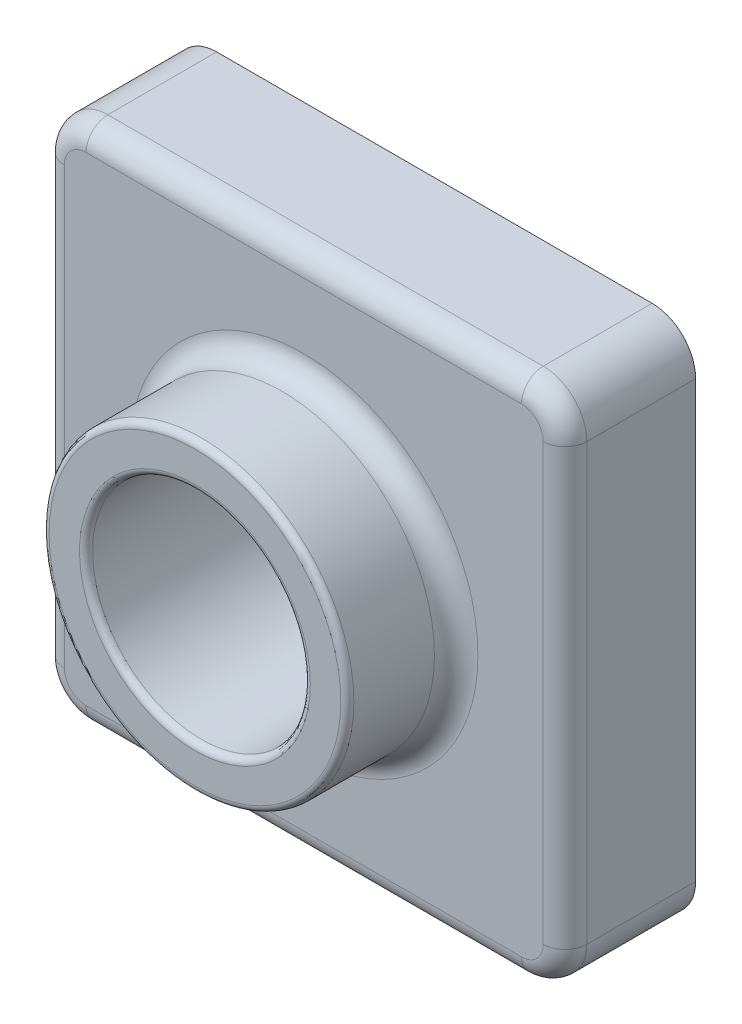
SolidWorks part; units mm, degrees
ref_plane "Front Plane" through (0, 0, 0) normal (0, 0, 1) x (1, 0, 0)
ref_plane "Top Plane" through (0, 0, 0) normal (0, 1, 0) x (1, 0, 0)
ref_plane "Right Plane" through (0, 0, 0) normal (1, 0, 0) x (0, 0, -1)
sketch "Sketch1" plane through (0, 0, 0) normal (0, 0, 1) x (1, 0, 0)
  line L0 (0, 60) -> (0, -60) construction
  line L1 (-60, 60) -> (60, 60)
  line L2 (-60, 60) -> (-60, -60)
  line L3 (-60, -60) -> (60, -60)
  line L4 (60, 60) -> (60, -60)
  line L6 (-60, 0) -> (60, 0) construction
  dimension "D1" = 120
  dimension "D2" = 120
extrude "Boss-Extrude1" add sketch "Sketch1" along normal blind 30
sketch "Sketch2" plane through (0, 0, 30) normal (0, 0, 1) x (1, 0, 0)
  circle A0 centre (0, 0) radius 35
  dimension "D1" = 70
extrude "Boss-Extrude2" add sketch "Sketch2" along normal blind 25
sketch "Sketch3" plane through (0, 0, 55) normal (0, 0, 1) x (1, 0, 0)
  circle A0 centre (0, 0) radius 25
  dimension "D1" = 50
extrude "Cut-Extrude1" cut sketch "Sketch3" against normal blind 76
fillet "Fillet1" radius 5 5 edges at (0, 60, 30) (60, 0, 30) (0, -60, 30) (-60, 0, 30) (35, 0, 30)
fillet "Fillet2" radius 1.5 2 edges at (35, 0, 55) (25, 0, 55)
fillet "Fillet4" radius 10 8 edges at (-58.5355, -58.5355, 28.5355) (58.5355, -58.5355, 28.5355) (58.5355, 58.5355, 28.5355) (-58.5355, 58.5355, 28.5355) (-60, 60, 12.5) (60, 60, 12.5) (60, -60, 12.5) (-60, -60, 12.5)
shell "Shell2" thickness 2 removed face at (25, 0, 0)
